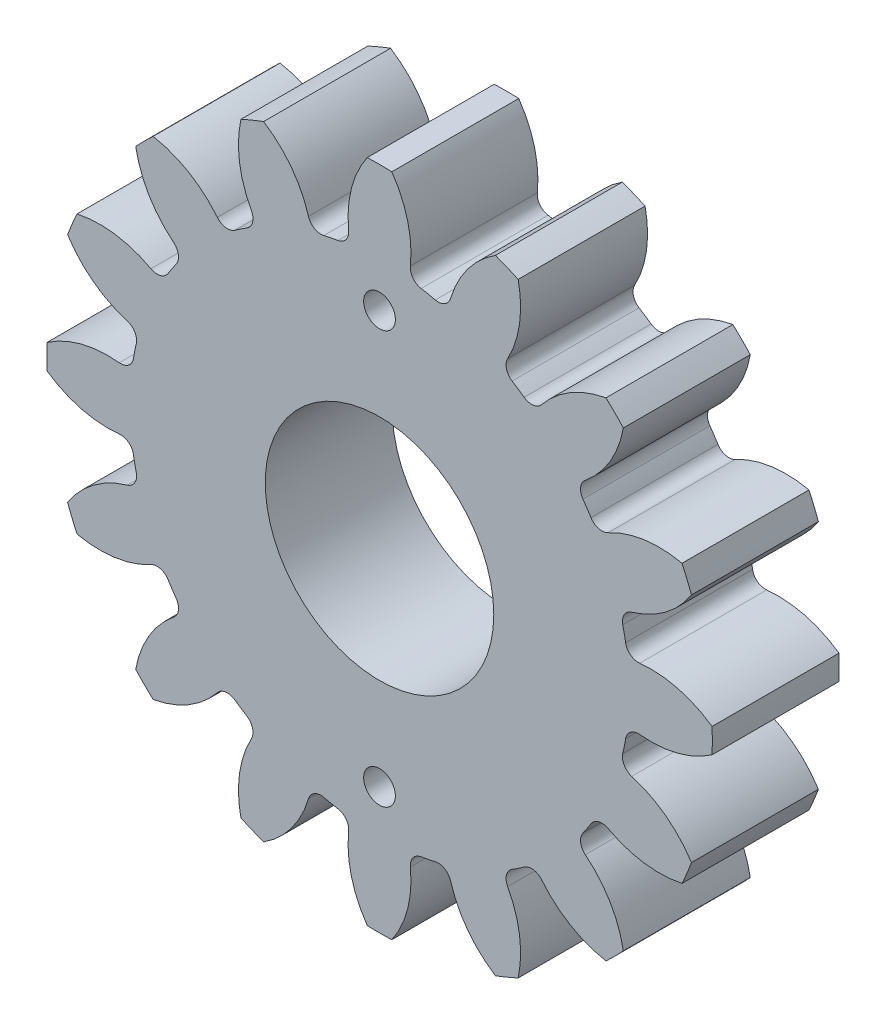
SolidWorks part; units mm, degrees
material "ABS"
ref_plane "Plane1" through (0, 0, 0) normal (0, 0, 1) x (1, 0, 0)
ref_plane "Plane2" through (0, 0, 0) normal (0, 1, 0) x (1, 0, 0)
ref_plane "Plane3" through (0, 0, 0) normal (1, 0, 0) x (0, 0, -1)
sketch "Esquisse1" plane through (0, 0, 0) normal (0, 0, 1) x (1, 0, 0)
  circle A0 centre (0, 0) radius 1.15
  dimension "D1" = 2.3
extrude "Base-Extrusion" add sketch "Esquisse1" along normal blind 2.5
sketch "Parametres" plane through (0, 0, 2.5) normal (0, 0, 1) x (1, 0, 0)
  line L0 (-33.4711, 41.7411) -> (-17.4711, 41.7411)
  line L1 (-33.4711, 34.0759) -> (-32.3061, 34.0759)
  line L2 (-33.4711, 23.0892) -> (-13.4711, 23.0892)
  line L3 (-33.4711, -2.6579) -> (-33.1221, -2.6579)
  line L4 (-38.9094, -12.5583) -> (-35.7678, -12.5583)
  line L5 (-48.8826, -19.2556) -> (-39.5626, -19.2556)
  line L6 (-48.8826, -29.9283) -> (-38.3976, -29.9283)
  line L7 (-48.8826, -38.2322) -> (-41.0188, -38.2322)
  line L8 (-48.8826, -45.1309) -> (-40.1246, -45.1309)
  line L9 (-48.8826, -60.7647) -> (-47.0526, -60.7647)
  line L10 (-48.8826, -76.1039) -> (-46.9019, -76.1039)
  line L11 (-48.8826, -88.0795) -> (-48.3004, -88.0795)
  line L12 (-50.5648, -98.8973) -> (-51.3404, -98.8973)
  line L13 (16.9123, -61.9871) -> (28.1623, -61.9871)
  line L14 (18.5152, -81.0212) -> (31.4731, -81.0212)
  line L15 (8.671, -96.0481) -> (4.433, -96.0481)
  line L16 (-33.4711, 13.8609) -> (-21.4711, 13.8609)
sketch "Esquisse3" plane through (0, 0, 0) normal (0, 0, 1) x (1, 0, 0)
  line L0 (0, 0) -> (0, 29.3764) construction
  line L1 (-1.5341, 7.7127) -> (0, 0)
  line L2 (0, 0) -> (1.5341, 7.7127)
  line L3 (0, 0) -> (0.9882, 8.702) construction
  line L4 (0, 0) -> (0.3877, 10.4778) construction
  line L5 (0, 0) -> (0.9135, 9.2751) construction
  arc A0 (0.3877, 10.4778) -> (0.908, 7.8112) centre (-2.3706, 8.5556) cw
  arc A1 (-0.3877, 10.4778) -> (-0.908, 7.8112) centre (2.3706, 8.5556) ccw
  arc A2 (1.5341, 7.7127) -> (0.908, 7.8112) centre (0, 0) ccw
  arc A3 (-1.5341, 7.7127) -> (-0.908, 7.8112) centre (0, 0) cw
  arc A4 (0.3877, 10.4778) -> (-0.3877, 10.4778) centre (0, 0) ccw
  dimension "D4" = 22.5
  dimension "D5" = 8.7579
  dimension "D6" = 9.32
  dimension "D1" = 10.485
  dimension "D2" = 6.479
  dimension "D3" = 5.625
  dimension "D7" = 2.119
  dimension "D8" = 7.8638
extrude "Boss.-Extru.1" add sketch "Esquisse3" along normal blind 4
fillet "Congé1" radius 0.4078 2 edges at (0.908, 7.8112, 2) (-0.908, 7.8112, 2)
ref_axis "Axe1" through (0, 0, 54) along (0, 0, -1)
pattern_circular "Répétition circulaire4" count 16 every 22.5 about axis through (0, 0, 54) along (0, 0, -1) of "Boss.-Extru.1", "Congé1"
sketch "Esquisse8" plane through (0, 0, 4) normal (0, 0, 1) x (1, 0, 0)
  circle A0 centre (0, 0) radius 3.6
  dimension "D1" = 7.2
extrude "Enlèv. mat.-Extru.1" cut sketch "Esquisse8" against normal through all
sketch "Esquisse9" plane through (0, 0, 0) normal (0, 0, -1) x (-1, 0, 0)
  line L0 (0, 6.5) -> (0, -6.5) construction
  circle A0 centre (0, 6.5) radius 0.5
  circle A1 centre (0, -6.5) radius 0.5
  dimension "D2" = 1
  dimension "D1" = 13
extrude "Enlèv. mat.-Extru.2" cut sketch "Esquisse9" against normal through all
equation "\"PI@Parametres\" = 3.141592654"
equation "\"Alpha_rad@Parametres\" = \"Alpha@Parametres\"*\"PI@Parametres\"/180"
equation "\"R@Parametres\" = \"Z@Parametres\"*\"m@Parametres\"/2"
equation "\"RT@Parametres\" = \"R@Parametres\"+\"m@Parametres\""
equation "\"RP@Parametres\" = \"R@Parametres\"-1.25*\"m@Parametres\""
equation "\"Rb@Parametres\" = \"R@Parametres\"*cos(\"Alpha_rad@Parametres\")"
equation "\"E@Parametres\" = \"PI@Parametres\"*\"R@Parametres\"/\"Z@Parametres\""
equation "\"Eb@Parametres\" = \"Rb@Parametres\"*((\"PI@Parametres\"*\"m@Parametres\"/(2*\"R@Parametres\"))+2*(tan(\"Alpha_rad@Parametres\")-\"Alpha_rad@Parametres\"))"
equation "\"As@Parametres\" = atn(sqr(\"RT@Parametres\"*\"RT@Parametres\"-\"Rb@Parametres\"*\"Rb@Parametres\")/\"Rb@Parametres\")"
equation "\"Et@Parametres\" = \"RT@Parametres\"*((\"E@Parametres\"/\"R@Parametres\")+2*(tan(\"Alpha_rad@Parametres\")-\"Alpha_rad@Parametres\"-tan(\"As@Parametres\")+\"As@Parametres\"))"
equation "\"Ap@Parametres\" = (\"E@Parametres\"/\"R@Parametres\")*180/\"PI@Parametres\""
equation "\"Ab@Parametres\" = (\"Eb@Parametres\"/\"Rb@Parametres\")*180/\"PI@Parametres\""
equation "\"At@Parametres\" = (\"Et@Parametres\"/\"RT@Parametres\")*180/\"PI@Parametres\""
equation "\"D7@Esquisse3\" = \"At@Parametres\"/2"
equation "\"D3@Esquisse3\"=\"Ap@Parametres\"/2"
equation "\"D2@Esquisse3\"=\"Ab@Parametres\"/2"
equation "\"D5@Esquisse3\"=\"Rb@Parametres\""
equation "\"D6@Esquisse3\"=\"R@Parametres\""
equation "\"D1@Esquisse3\"=\"RT@Parametres\""
equation "\"D4@Esquisse3\" = \"Ap@Parametres\"*2"
equation "\"D1@Congé1\" = 0.35*\"m@Parametres\""
equation "\"D2@Répétition circulaire4\" = \"Ap@Parametres\"*2"
equation "\"D1@Répétition circulaire4\" = \"Z@Parametres\""
equation "\"D8@Esquisse3\" = \"RP@Parametres\""
